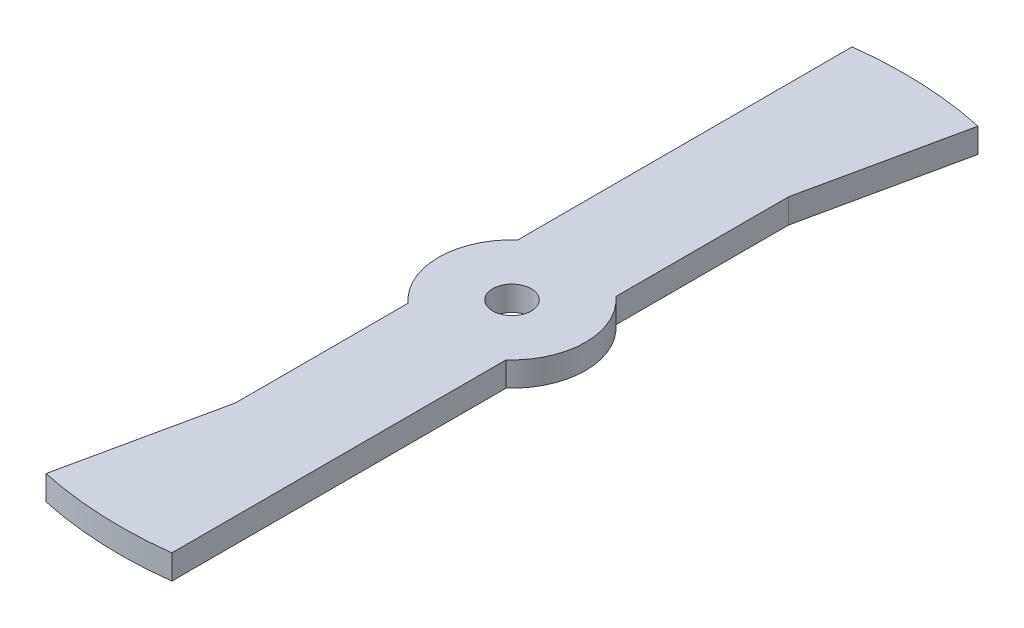
SolidWorks part; units mm, degrees
material "AISI 316 Stainless Steel Sheet (SS)"
ref_plane "Front Plane" through (0, 0, 0) normal (0, 0, 1) x (1, 0, 0)
ref_plane "Top Plane" through (0, 0, 0) normal (0, 1, 0) x (1, 0, 0)
ref_plane "Right Plane" through (0, 0, 0) normal (1, 0, 0) x (0, 0, -1)
sketch "Sketch1" plane through (0, 0, 0) normal (0, 1, 0) x (1, 0, 0)
  line L0 (0, 19.05) -> (0, 101.6) construction
  line L1 (-12.7, 100.8031) -> (-12.7, 14.199)
  line L2 (12.7, 14.199) -> (12.7, 58.973)
  line L3 (12.7, 58.973) -> (21.3895, 99.323)
  line L4 (12.7, -100.8031) -> (12.7, -14.199)
  line L5 (-12.7, -58.973) -> (-21.3895, -99.323)
  line L6 (-12.7, -14.199) -> (-12.7, -58.973)
  circle A1 centre (0, 0) radius 19.05 construction
  circle A2 centre (0, 0) radius 101.6 construction
  arc A3 (-12.7, 100.8031) -> (21.3895, 99.323) centre (0, 0) cw
  circle A4 centre (0, 0) radius 60.325 construction
  arc A5 (12.7, -100.8031) -> (-21.3895, -99.323) centre (0, 0) cw
  arc A6 (-12.7, 14.199) -> (-12.7, -14.199) centre (0, 0) ccw
  arc A7 (12.7, 14.199) -> (12.7, -14.199) centre (0, 0) cw
  point P9 (12.7, 14.199)
  point P15 (0, 60.325)
  point P23 (0, 0)
  dimension "D2" = 38.1
  dimension "D3" = 203.2
  dimension "D4" = 25.4
  dimension "D6" = 2
extrude "Boss-Extrude1" add sketch "Sketch1" along normal blind 6.35 contours A7 L2 L3 A3 L1 A6 L6 L5 A5 L4 region at (0, 0, 0)
sketch "Sketch2" plane through (0, 6.35, 0) normal (0, 1, 0) x (1, 0, 0)
  circle A0 centre (0, 0) radius 5
  dimension "D1" = 10
extrude "Cut-Extrude1" cut sketch "Sketch2" against normal blind 9.144
